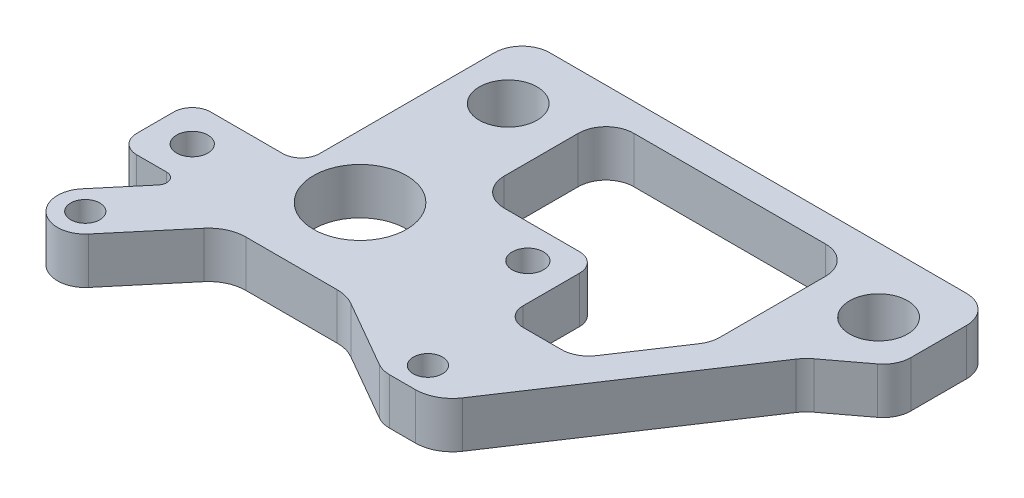
SolidWorks part; units mm, degrees
other "Markup1"
sketch "Sketch6" plane through (-23.3268, 0, -30.7975) normal (-0.0348, 0.9994, -0.0028) x (-0.9993, -0.0348, 0.0153)
sketch "Sketch7" plane through (-23.3268, 0, -30.7975) normal (-0.0348, 0.9994, -0.0028) x (-0.9993, -0.0348, 0.0153)
sketch "Sketch8" plane through (-23.3268, 0, -30.7975) normal (-0.0348, 0.9994, -0.0028) x (-0.9993, -0.0348, 0.0153)
sketch "Sketch10" plane through (-23.3268, 0, -30.7975) normal (-0.0348, 0.9994, -0.0028) x (-0.9993, -0.0348, 0.0153)
sketch "Sketch13" plane through (-23.3268, 0, -30.7975) normal (-0.0348, 0.9994, -0.0028) x (-0.9993, -0.0348, 0.0153)
sketch "Sketch15" plane through (-23.3268, 0, -30.7975) normal (-0.0348, 0.9994, -0.0028) x (-0.9993, -0.0348, 0.0153)
sketch "Sketch16" [suppressed] plane through (-23.3268, 0, -30.7975) normal (-0.0348, 0.9994, -0.0028) x (-0.9993, -0.0348, 0.0153)
sketch "Sketch17" plane through (-23.3268, 0, -30.7975) normal (-0.0348, 0.9994, -0.0028) x (-0.9993, -0.0348, 0.0153)
sketch "Sketch18" plane through (-23.3268, 0, -30.7975) normal (-0.0348, 0.9994, -0.0028) x (-0.9993, -0.0348, 0.0153)
sketch "Sketch19" [suppressed] plane through (-23.3268, 0, -30.7975) normal (-0.0348, 0.9994, -0.0028) x (-0.9993, -0.0348, 0.0153)
sketch "Sketch21" plane through (-23.3268, 0, -30.7975) normal (-0.0348, 0.9994, -0.0028) x (-0.9993, -0.0348, 0.0153)
sketch "Sketch23" plane through (-23.3268, 0, -30.7975) normal (-0.0348, 0.9994, -0.0028) x (-0.9993, -0.0348, 0.0153)
sketch "Sketch24" plane through (-23.3268, 0, -30.7975) normal (-0.0348, 0.9994, -0.0028) x (-0.9993, -0.0348, 0.0153)
sketch "Sketch25" plane through (-23.3268, 0, -30.7975) normal (-0.0348, 0.9994, -0.0028) x (-0.9993, -0.0348, 0.0153)
sketch "Sketch26" [suppressed] plane through (-23.3268, 0, -30.7975) normal (-0.0348, 0.9994, -0.0028) x (-0.9993, -0.0348, 0.0153)
sketch "Sketch27" plane through (-23.3268, 0, -30.7975) normal (-0.0348, 0.9994, -0.0028) x (-0.9993, -0.0348, 0.0153)
sketch "Sketch28" plane through (-23.3268, 0, -30.7975) normal (-0.0348, 0.9994, -0.0028) x (-0.9993, -0.0348, 0.0153)
sketch "Sketch29" plane through (-23.3268, 0, -30.7975) normal (-0.0348, 0.9994, -0.0028) x (-0.9993, -0.0348, 0.0153)
sketch "Sketch30" plane through (-23.3268, 0, -30.7975) normal (-0.0348, 0.9994, -0.0028) x (-0.9993, -0.0348, 0.0153)
sketch "Sketch32" plane through (-23.3268, 0, -30.7975) normal (-0.0348, 0.9994, -0.0028) x (-0.9993, -0.0348, 0.0153)
sketch "Sketch34" [suppressed] plane through (-23.3268, 0, -30.7975) normal (-0.0348, 0.9994, -0.0028) x (-0.9993, -0.0348, 0.0153)
sketch "Sketch35" [suppressed] plane through (-23.3268, 0, -30.7975) normal (-0.0348, 0.9994, -0.0028) x (-0.9993, -0.0348, 0.0153)
sketch "Sketch36" [suppressed] plane through (-23.3268, 0, -30.7975) normal (-0.0348, 0.9994, -0.0028) x (-0.9993, -0.0348, 0.0153)
sketch "Sketch37" plane through (-23.3268, 0, -30.7975) normal (-0.0348, 0.9994, -0.0028) x (-0.9993, -0.0348, 0.0153)
sketch "Sketch38" plane through (-23.3268, 0, -30.7975) normal (-0.0348, 0.9994, -0.0028) x (-0.9993, -0.0348, 0.0153)
sketch "Sketch39" [suppressed] plane through (-23.3268, 0, -30.7975) normal (-0.0348, 0.9994, -0.0028) x (-0.9993, -0.0348, 0.0153)
sketch "Sketch40" plane through (-23.3268, 0, -30.7975) normal (-0.0348, 0.9994, -0.0028) x (-0.9993, -0.0348, 0.0153)
sketch "Sketch41" plane through (-23.3268, 0, -30.7975) normal (-0.0348, 0.9994, -0.0028) x (-0.9993, -0.0348, 0.0153)
sketch "Sketch42" plane through (-23.3268, 0, -30.7975) normal (-0.0348, 0.9994, -0.0028) x (-0.9993, -0.0348, 0.0153)
sketch "Sketch43" plane through (-23.3268, 0, -30.7975) normal (-0.0348, 0.9994, -0.0028) x (-0.9993, -0.0348, 0.0153)
sketch "Sketch44" plane through (-23.3268, 0, -30.7975) normal (-0.0348, 0.9994, -0.0028) x (-0.9993, -0.0348, 0.0153)
sketch "Sketch45" plane through (-23.3268, 0, -30.7975) normal (-0.0348, 0.9994, -0.0028) x (-0.9993, -0.0348, 0.0153)
sketch "Sketch46" plane through (-23.3268, 0, -30.7975) normal (-0.0348, 0.9994, -0.0028) x (-0.9993, -0.0348, 0.0153)
sketch "Sketch47" plane through (-23.3268, 0, -30.7975) normal (-0.0348, 0.9994, -0.0028) x (-0.9993, -0.0348, 0.0153)
sketch "Sketch48" plane through (-23.3268, 0, -30.7975) normal (-0.0348, 0.9994, -0.0028) x (-0.9993, -0.0348, 0.0153)
sketch "Sketch49" plane through (-23.3268, 0, -30.7975) normal (-0.0348, 0.9994, -0.0028) x (-0.9993, -0.0348, 0.0153)
sketch "Sketch50" plane through (-23.3268, 0, -30.7975) normal (-0.0348, 0.9994, -0.0028) x (-0.9993, -0.0348, 0.0153)
sketch "Sketch51" plane through (-23.3268, 0, -30.7975) normal (-0.0348, 0.9994, -0.0028) x (-0.9993, -0.0348, 0.0153)
sketch "Sketch52" [suppressed] plane through (-23.3268, 0, -30.7975) normal (-0.0348, 0.9994, -0.0028) x (-0.9993, -0.0348, 0.0153)
sketch "Sketch53" [suppressed] plane through (-23.3268, 0, -30.7975) normal (-0.0348, 0.9994, -0.0028) x (-0.9993, -0.0348, 0.0153)
sketch "Sketch54" [suppressed] plane through (-23.3268, 0, -30.7975) normal (-0.0348, 0.9994, -0.0028) x (-0.9993, -0.0348, 0.0153)
sketch "Sketch55" [suppressed] plane through (-23.3268, 0, -30.7975) normal (-0.0348, 0.9994, -0.0028) x (-0.9993, -0.0348, 0.0153)
sketch "Sketch56" plane through (-23.3268, 0, -30.7975) normal (-0.0348, 0.9994, -0.0028) x (-0.9993, -0.0348, 0.0153)
sketch "Sketch57" plane through (-23.3268, 0, -30.7975) normal (-0.0348, 0.9994, -0.0028) x (-0.9993, -0.0348, 0.0153)
sketch "Sketch58" plane through (-23.3268, 0, -30.7975) normal (-0.0348, 0.9994, -0.0028) x (-0.9993, -0.0348, 0.0153)
sketch "Sketch59" plane through (-23.3268, 0, -30.7975) normal (-0.0348, 0.9994, -0.0028) x (-0.9993, -0.0348, 0.0153)
sketch "Sketch60" plane through (-23.3268, 0, -30.7975) normal (-0.0348, 0.9994, -0.0028) x (-0.9993, -0.0348, 0.0153)
sketch "Sketch61" plane through (-23.3268, 0, -30.7975) normal (-0.0348, 0.9994, -0.0028) x (-0.9993, -0.0348, 0.0153)
sketch "Sketch62" [suppressed] plane through (-23.3268, 0, -30.7975) normal (-0.0348, 0.9994, -0.0028) x (-0.9993, -0.0348, 0.0153)
sketch "Sketch63" [suppressed] plane through (-23.3268, 0, -30.7975) normal (-0.0348, 0.9994, -0.0028) x (-0.9993, -0.0348, 0.0153)
sketch "Sketch64" plane through (-24.0303, 0, -30.7975) normal (-0.0348, 0.9994, -0.0028) x (-0.9993, -0.0348, 0.0153)
sketch "Sketch65" plane through (-24.0303, 0, -30.7975) normal (-0.0348, 0.9994, -0.0028) x (-0.9993, -0.0348, 0.0153)
sketch "Sketch66" plane through (-24.0303, 0, -30.7975) normal (-0.0348, 0.9994, -0.0028) x (-0.9993, -0.0348, 0.0153)
sketch "Sketch67" [suppressed] plane through (-24.0303, 0, -30.7975) normal (-0.0348, 0.9994, -0.0028) x (-0.9993, -0.0348, 0.0153)
sketch "Sketch68" plane through (-24.0303, 0, -30.7975) normal (-0.0348, 0.9994, -0.0028) x (-0.9993, -0.0348, 0.0153)
sketch "Sketch69" plane through (-24.0303, 0, -30.7975) normal (-0.0348, 0.9994, -0.0028) x (-0.9993, -0.0348, 0.0153)
sketch "Sketch70" plane through (-24.0303, 0, -30.7975) normal (-0.0348, 0.9994, -0.0028) x (-0.9993, -0.0348, 0.0153)
sketch "Sketch71" plane through (-24.0303, 0, -30.7975) normal (-0.0348, 0.9994, -0.0028) x (-0.9993, -0.0348, 0.0153)
sketch "Sketch72" plane through (-24.0303, 0, -30.7975) normal (-0.0348, 0.9994, -0.0028) x (-0.9993, -0.0348, 0.0153)
sketch "Sketch73" [suppressed] plane through (-23.3268, 0, -30.7975) normal (-0.0348, 0.9994, -0.0028) x (-0.9993, -0.0348, 0.0153)
sketch "Sketch74" [suppressed] plane through (-24.0303, 0, -30.7975) normal (-0.0348, 0.9994, -0.0028) x (-0.9993, -0.0348, 0.0153)
sketch "Sketch75" [suppressed] plane through (-24.0303, 0, -30.7975) normal (-0.0348, 0.9994, -0.0028) x (-0.9993, -0.0348, 0.0153)
sketch "Sketch76" [suppressed] plane through (-24.0303, 0, -30.7975) normal (-0.0348, 0.9994, -0.0028) x (-0.9993, -0.0348, 0.0153)
sketch "Sketch77" plane through (-24.0303, 0, -30.7975) normal (-0.0348, 0.9994, -0.0028) x (-0.9993, -0.0348, 0.0153)
sketch "Sketch78" plane through (-23.5217, 0, -30.7975) normal (-0.0348, 0.9994, -0.0028) x (-0.9993, -0.0348, 0.0153)
material "6061-T6 (SS)"
ref_plane "X-Y Datum" through (0, 0, 0) normal (0, 0, 1) x (1, 0, 0)
ref_plane "X-Z Datum" through (0, 0, 0) normal (0, 1, 0) x (1, 0, 0)
ref_plane "Y-Z Datum" through (0, 0, 0) normal (1, 0, 0) x (0, 0, -1)
other "Graphic1"
other "Graphic (Closed) -1"
other "Graphic (Closed) -2"
sketch "Sketch2" plane through (0, 0, 0) normal (0, 1, 0) x (1, 0, 0)
  line L0 (48.6426, -18.7325) -> (-23.0162, -18.7325)
  line L1 (24.0125, -14.7036) -> (25.7865, -13.7801) construction
  line L2 (0, 0) -> (105.5557, -202.7707) construction
  line L3 (11.142, -21.4036) -> (-3.5026, -29.027) construction
  line L4 (0, 0) -> (0, -121.3797) construction
  line L5 (-3.5026, -29.027) -> (90.9112, -210.3941) construction
  line L6 (90.9112, -210.3941) -> (105.5557, -202.7707) construction
  line L7 (11.142, -21.4036) -> (24.0125, -14.7036) construction
  line L11 (-12.7, 30.7975) -> (57.15, 30.7975)
  line L12 (57.15, 13.0175) -> (57.15, 30.7975)
  line L13 (57.15, 13.0175) -> (-12.7, 13.0175) construction
  line L15 (44.7685, -18.0975) -> (44.7685, -11.3157) construction
  line L16 (44.7685, -18.0975) -> (34.8625, -18.0975) construction
  line L18 (44.7685, 9.8425) -> (34.8625, 9.8425) construction
  line L20 (44.7685, -11.3157) -> (49.8485, -11.3157) construction
  line L21 (49.8485, -11.3157) -> (49.8485, 3.0607) construction
  line L22 (49.8485, 3.0607) -> (44.7685, 3.0607) construction
  line L23 (44.7685, 3.0607) -> (44.7685, 9.8425) construction
  line L24 (34.8625, -18.0975) -> (34.8625, 9.8425) construction
  line L25 (48.6426, -18.7325) -> (57.15, 13.0175)
  line L26 (-12.7, 30.7975) -> (-12.7, 13.0175)
  line L28 (-12.5603, 0) -> (-16.51, -40.5272) construction
  line L30 (-23.0162, -18.7325) -> (-12.7, 13.0175)
  circle A0 centre (0, 0) radius 3.175
  circle A1 centre (24.0125, -14.7036) radius 2
  circle A2 centre (-1.5875, 21.9075) radius 3.9688
  circle A3 centre (49.2125, 21.9075) radius 3.9687
  circle A4 centre (39.8485, -4.1275) radius 5.1
  circle A5 centre (24.0125, -14.7036) radius 3.175 construction
  circle A6 centre (39.8485, -14.6275) radius 1.6
  circle A7 centre (39.8485, 6.3725) radius 1.6
  circle A8 centre (-17.2047, -14.9225) radius 3.175 construction
  circle A9 centre (-17.2047, -14.9225) radius 2
  point P9 (11.142, -21.4036)
  point P30 (49.8485, -4.1275)
  point P31 (34.8625, -4.1275)
  dimension "D1" = 6.35
  dimension "D8" = 4
  dimension "D10" = 7.9375
  dimension "D11" = 7.9375
  dimension "D16" = 27.94
  dimension "D23" = 10.2
  dimension "D20" = 6.35
  dimension "D30" = 3.2
  dimension "D32" = 3.2
  dimension "D34" = 6.35
  dimension "D35" = 4
  dimension "D3" = 13.0175
  dimension "D4" = 16.51
  dimension "D5" = 228.6
  dimension "D6" = 24.13
  dimension "D7" = 27.5
  dimension "D9" = 16.51
  dimension "D12" = 8.89
  dimension "D13" = 69.85
  dimension "D14" = 7.9375
  dimension "D15" = 31.75
  dimension "D17" = 17.78
  dimension "D18" = 3.175
  dimension "D19" = 14.986
  dimension "D21" = 5.08
  dimension "D22" = 14.3764
  dimension "D24" = 10
  dimension "D25" = 36.83
  dimension "D26" = 50.8
  dimension "D27" = 165
  dimension "D28" = 12.7
  dimension "D29" = 17.3015
  dimension "D31" = 10.5
  dimension "D33" = 10.5
  dimension "D36" = 162
extrude "Boss-Extrude1" [suppressed] add sketch "Sketch2" against normal blind 6.35
ref_point "Point1" [suppressed]
sketch "Sketch3" [suppressed] plane through (0, 0, 0) normal (0, 1, 0) x (1, 0, 0)
  line L0 (39.9681, 6.3725) -> (39.9681, -4.1275) construction
  line L1 (57.2697, 12.9663) -> (-12.5803, 12.9663) construction
  line L5 (39.9681, -4.1275) -> (39.9681, -14.6275) construction
  line L6 (42.0297, -18.7325) -> (20.4164, -18.7325)
  line L7 (57.2697, 12.9663) -> (57.2697, 30.7975)
  line L8 (57.2697, 30.7975) -> (-12.5803, 30.7975)
  line L9 (-12.5803, 30.7975) -> (-12.5803, 12.9663)
  line L10 (40.938, 24.6176) -> (16.9472, 10.7666)
  line L11 (13.3942, 11.8528) -> (6.9035, 25.1608)
  line L12 (8.045, 26.9875) -> (40.303, 26.9875)
  line L13 (57.2697, 12.9663) -> (48.3797, 12.9663)
  line L14 (48.3797, 12.9663) -> (48.3797, -12.3825)
  line L16 (-23.0162, -18.7325) -> (48.6426, -18.7325) construction
  line L18 (16.6064, -14.8627) -> (10.2787, -14.8627)
  line L21 (-8.965, -15.5427) -> (-15.106, -18.7325)
  line L24 (-21.1701, -13.6017) -> (-12.5803, 12.9663)
  line L29 (17.8764, -16.1925) -> (17.8764, -16.1327)
  circle A0 centre (0.1197, 0) radius 3.175
  circle A1 centre (-1.4678, 21.9075) radius 3.9688
  circle A2 centre (49.3322, 21.9075) radius 3.9687
  circle A3 centre (39.9681, -4.1275) radius 5.1
  circle A4 centre (39.9681, -14.6275) radius 1.6
  circle A5 centre (39.9681, 6.3725) radius 1.6
  circle A6 centre (24.1322, -14.7036) radius 2
  circle A7 centre (-17.085, -14.9225) radius 2
  arc A8 (13.3942, 11.8528) -> (16.9472, 10.7666) centre (15.6772, 12.9663) ccw
  arc A9 (8.045, 26.9875) -> (6.9035, 25.1608) centre (8.045, 25.7175) ccw
  arc A10 (40.938, 24.6176) -> (40.303, 26.9875) centre (40.303, 25.7175) ccw
  arc A11 (10.2787, -14.8627) -> (-8.965, -15.5427) centre (0.1197, 0) cw
  arc A12 (-15.106, -18.7325) -> (-21.1701, -13.6017) centre (-17.085, -14.9225) cw
  arc A13 (42.0297, -18.7325) -> (48.3797, -12.3825) centre (42.0297, -12.3825) ccw
  arc A14 (20.4164, -18.7325) -> (17.8764, -16.1925) centre (20.4164, -16.1925) cw
  arc A15 (16.6064, -14.8627) -> (17.8764, -16.1327) centre (16.6064, -16.1327) cw
  dimension "D1" = 6.35
  dimension "D4" = 7.9375
  dimension "D9" = 10.2
  dimension "D10" = 3.2
  dimension "D11" = 4
  dimension "D21" = 2.54
  dimension "D22" = 1.27
  dimension "D3" = 6.35
  dimension "D28" = 2.54
  dimension "D29" = 1.27
  dimension "D2" = 7.9375
  dimension "D5" = 50.8
  dimension "D6" = 21.9075
  dimension "D7" = 1.5875
  dimension "D8" = 8.89
  dimension "D12" = 10.5
  dimension "D13" = 17.2047
  dimension "D14" = 24.0125
  dimension "D15" = 14.7036
  dimension "D16" = 39.8485
  dimension "D17" = 4.1275
  dimension "D18" = 14.9225
  dimension "D19" = 69.85
  dimension "D20" = 3.81
  dimension "D23" = 30
  dimension "D24" = 64
  dimension "D25" = 32.258
  dimension "D26" = 15.5575
  dimension "D27" = 25.3488
  dimension "D30" = 8.89
sketch "Sketch4" plane through (0, 0, 0) normal (0, 1, 0) x (1, 0, 0)
  line L0 (39.8485, 6.3725) -> (39.8485, -4.1275) construction
  line L1 (56.1975, 13.0175) -> (-8.5725, 13.0175) construction
  line L2 (39.8485, -4.1275) -> (39.8485, -14.6275) construction
  line L3 (28.7355, -18.4375) -> (22.4839, -18.4375)
  line L5 (52.3875, 30.7975) -> (-4.7625, 30.7975)
  line L6 (-8.5725, 26.9875) -> (-8.5725, 12.6075)
  line L43 (48.9856, 12.0279) -> (54.6804, 16.3193)
  line L44 (56.1975, 19.3621) -> (56.1975, 26.9875)
  line L50 (-17.3145, -25.274) -> (-23.148, -20.3714)
  line L58 (20.5837, -17.9298) -> (10.1629, -11.9335)
  line L59 (0, 0) -> (0, 5.6144) construction
  line L64 (48.9856, 12.0279) -> (28.7355, -18.4375)
  line L65 (6.7496, 26.9875) -> (40.693, 26.9875)
  line L66 (6.7496, 26.9875) -> (6.7496, 9.2075)
  line L70 (33.289, -3.6663) -> (40.693, 7.4726)
  line L74 (40.693, 26.9875) -> (40.693, 7.4726)
  line L75 (6.7496, 9.2075) -> (23.453, 9.2075)
  line L76 (10.1629, -11.9335) -> (-6.1031, -11.9335)
  line L77 (-6.1031, -11.9335) -> (-17.3145, -25.274)
  line L78 (-23.5217, 0.508) -> (-8.5725, 0.508)
  line L79 (-8.5725, 0.508) -> (-8.5725, 12.6075)
  line L82 (23.453, 9.2075) -> (23.453, -3.6663)
  line L83 (23.453, -3.6663) -> (33.289, -3.6663)
  line L85 (-14.1393, -9.652) -> (-23.148, -20.3714)
  line L86 (-23.5217, 0.508) -> (-23.5217, -9.652)
  line L88 (-23.5217, -9.652) -> (-14.1393, -9.652)
  line L89 (18.4417, 4.572) -> (-18.4417, -4.572)
  circle A0 centre (0, 0) radius 6.3881
  circle A1 centre (-1.5875, 21.9075) radius 3.9688
  circle A2 centre (49.2125, 21.9075) radius 3.9687
  circle A6 centre (24.0125, -14.7036) radius 2
  circle A7 centre (-17.78, -19.906) radius 2
  arc A19 (-8.5725, 26.9875) -> (-4.7625, 30.7975) centre (-4.7625, 26.9875) cw
  arc A20 (52.3875, 30.7975) -> (56.1975, 26.9875) centre (52.3875, 26.9875) cw
  circle A33 centre (24.0125, -14.7036) radius 3.5 construction
  arc A45 (56.1975, 19.3621) -> (54.6804, 16.3193) centre (52.3875, 19.3621) cw
  arc A53 (22.4839, -18.4375) -> (20.5837, -17.9298) centre (22.4839, -14.6275) cw
  circle A55 centre (0, 0) radius 19 construction
  circle A57 centre (18.4417, 4.572) radius 2.1463
  circle A58 centre (-18.4417, -4.572) radius 2.1463
  point P30 (21.466, -18.4375)
  point P36 (9.3466, -11.4637)
  point P49 (-17.78, -19.906)
  point P58 (-8.5725, 30.7975)
  point P77 (56.1975, 17.4625)
  dimension "D1" = 12.7762
  dimension "D2" = 7.9375
  dimension "D7" = 10.16
  dimension "D8" = 4
  dimension "D19" = 17.24
  dimension "D20" = 6.9738
  dimension "D25" = 3.81
  dimension "D26" = 7
  dimension "D27" = 209.917
  dimension "D31" = 4.2926
  dimension "D33" = 3.81
  dimension "D37" = 5.08
  dimension "D38" = 4.572
  dimension "D39" = 15.5045
  dimension "D48" = 17.78
  dimension "D23" = 3.81
  dimension "D32" = 3.81
  dimension "D46" = 5.08
  dimension "D47" = 19.906
  dimension "D45" = 3.81
  dimension "D18" = 17.78
  dimension "D29" = 3.81
  dimension "D30" = 38
  dimension "D34" = 12.8738
  dimension "D35" = 4.3845
  dimension "D41" = 33.9434
  dimension "D42" = 7.3154
  dimension "D43" = 42.731
  dimension "D44" = 4.572
  dimension "D15" = 3.81
  dimension "D3" = 50.8
  dimension "D4" = 21.9075
  dimension "D5" = 1.5875
  dimension "D9" = 10.5
  dimension "D10" = 24.0125
  dimension "D11" = 14.7036
  dimension "D12" = 39.8485
  dimension "D13" = 4.1275
  dimension "D14" = 3.81
  dimension "D16" = 6.985
  dimension "D17" = 8.89
  dimension "D21" = 17.78
  dimension "D22" = 229.956
  dimension "D24" = 236.388
  dimension "D28" = 30.4654
  dimension "D36" = 9.525
  dimension "D40" = 127
  dimension "D60" = 6.985
extrude "Boss-Extrude2" add sketch "Sketch4" against normal blind 6.35
ref_point "Point2"
ref_point "Point3"
ref_point "Point4"
other "Graphic2" [suppressed]
other "Graphic (Closed) -3"
other "Graphic (Closed) -4"
other "Graphic (Closed) -5"
fillet "Fillet1" radius 5.08 2 edges at (48.9856, -3.175, -12.0279) (28.7355, -3.175, 18.4375)
fillet "Fillet7" radius 3.81 4 edges at (6.7496, -3.175, -9.2075) (40.693, -3.175, -7.4726) (40.693, -3.175, -26.9875) (6.7496, -3.175, -26.9875)
fillet "Fillet9" radius 5.08 2 edges at (10.1629, -3.175, 11.9335) (-6.1031, -3.175, 11.9335)
fillet "Fillet10" radius 1.27 1 edges at (-14.1393, -3.175, 9.652)
fillet "Fillet11" radius 3.81 2 edges at (-17.3145, -3.175, 25.274) (-23.148, -3.175, 20.3714)
fillet "Fillet12" radius 2.54 5 edges at (23.453, -3.175, 3.6663) (23.453, -3.175, -9.2075) (-8.5725, -3.175, -0.508) (-23.5217, -3.175, -0.508) (-23.5217, -3.175, 9.652)
fillet "Fillet13" radius 3.81 1 edges at (33.289, -3.175, 3.6663)
